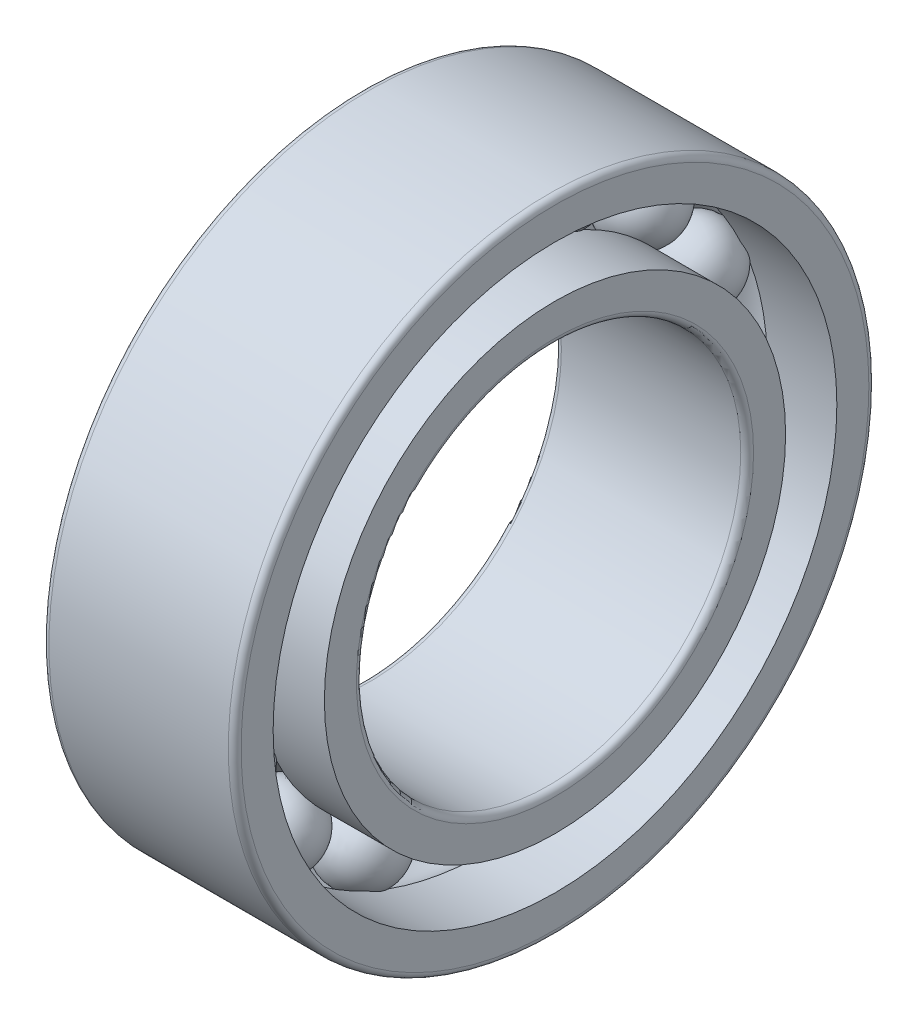
SolidWorks part; units mm, degrees
ref_plane "Plane1" through (0, 0, 0) normal (0, 0, 1) x (1, 0, 0)
ref_plane "Plane2" through (0, 0, 0) normal (0, 1, 0) x (1, 0, 0)
ref_plane "Plane3" through (0, 0, 0) normal (1, 0, 0) x (0, 0, -1)
sketch "Clipboard" plane through (0, 0, 0) normal (0, 0, 1) x (1, 0, 0)
  line L0 (-10, 0) -> (10, 0) construction
  line L1 (0, 0) -> (21.4945, -6.1634)
  line L2 (0, 0) -> (3.845, 1.1025)
  line L3 (0, 0) -> (21.4945, -6.1634)
  line L4 (0, 0) -> (-22.3573, -0.3902)
  dimension "BallCLRad" = 4
sketch "CagSpiSke" plane through (0, 0, 0) normal (0, 0, 1) x (1, 0, 0)
  line L0 (0.06, 3.9) -> (0.06, 4.1)
  line L1 (0.06, 4.1) -> (-0.06, 4.1)
  line L2 (-0.06, 4.1) -> (-0.06, 3.9)
  line L3 (-0.06, 3.9) -> (0.06, 3.9)
  line L4 (-20.6375, 0) -> (20.6375, 0) construction
  line L5 (0, 0) -> (0, 23.7692) construction
  dimension "OD" = 8.2
  dimension "ID" = 7.8
revolve "CageSpine" add sketch "CagSpiSke" angle 0.001 about L4 reverse direction yes
ref_axis "Axis1" through (-50, 0, 0) along (1, 0, 0)
sketch "CagBalSke" plane through (0, 0, 0) normal (0, 0, 1) x (1, 0, 0)
  line L0 (-0.66, 4) -> (0.66, 4)
  line L1 (-1.905, 4) -> (1.905, 4) construction
  line L2 (-10, 0) -> (10, 0) construction
  line L3 (0, 0) -> (0, 24) construction
  arc A0 (0.66, 4) -> (-0.66, 4) centre (0, 4) cw
  dimension "BallCLRad" = 4
revolve "CageBall" [suppressed] add sketch "CagBalSke" angle 360 about L1 reverse direction yes
pattern_circular "CageBalls" [suppressed] count 16 every 22.5 about axis through (-50, 0, 0) along (1, 0, 0)
sketch "CagTrmODSke" plane through (0, 0, 0) normal (0, 0, 1) x (1, 0, 0)
  line L0 (0.661, 4.1) -> (0.661, 4.661)
  line L1 (0.661, 4.661) -> (-0.661, 4.661)
  line L2 (-0.661, 4.661) -> (-0.661, 4.1)
  line L3 (-0.661, 4.1) -> (0.661, 4.1)
  line L4 (-20.6375, 0) -> (20.6375, 0) construction
  line L5 (0, 0) -> (0, 25) construction
  dimension "Width" = 1.322
  dimension "ID" = 8.2
  dimension "OD" = 9.322
revolve "CageTrimOD" [suppressed] cut sketch "CagTrmODSke" angle 360 about L4 reverse direction yes
sketch "CagTrmIDSke" plane through (0, 0, 0) normal (0, 0, 1) x (1, 0, 0)
  line L0 (0.661, 3.341) -> (0.661, 3.9)
  line L1 (0.661, 3.9) -> (-0.661, 3.9)
  line L2 (-0.661, 3.9) -> (-0.661, 3.341)
  line L3 (-0.661, 3.341) -> (0.661, 3.341)
  line L4 (-20.6375, 0) -> (20.6375, 0) construction
  line L5 (0, 0) -> (0, 25) construction
  dimension "Width" = 1.322
  dimension "ID" = 6.682
  dimension "OD" = 7.8
revolve "CageTrimID" [suppressed] cut sketch "CagTrmIDSke" angle 360 about L4 reverse direction yes
sketch "BalSimSke" plane through (0, 0, 0) normal (0, 0, 1) x (1, 0, 0)
  line L0 (-10, 0) -> (10, 0) construction
  line L1 (-10, 4) -> (10, 4) construction
  line L2 (0, 0) -> (0, 23) construction
  circle A0 centre (0, 4) radius 0.6
  dimension "BallCLRad" = 4
  dimension "Ball_diameter" = 1.2
revolve "BallsSimplified" [suppressed] add sketch "BalSimSke" angle 360 about L0
sketch "BalDetSke" plane through (0, 0, 0) normal (0, 0, 1) x (1, 0, 0)
  line L0 (-0.6, 4) -> (0.6, 4)
  line L1 (-1.905, 4) -> (1.905, 4) construction
  line L2 (0, 0) -> (0, 25) construction
  arc A0 (0.6, 4) -> (-0.6, 4) centre (0, 4) cw
  dimension "BallCLRad" = 4
  dimension "Ball_diameter" = 1.2
revolve "BallDetailed" add sketch "BalDetSke" angle 360 about L1 reverse direction yes
sketch "InnRacSke" plane through (0, 0, 0) normal (0, 0, 1) x (1, 0, 0)
  line L0 (-0.4131, 3.6) -> (-1.5, 3.6)
  line L1 (-1.5, 3.6) -> (-1.5, 3.1)
  line L2 (-1.4, 3) -> (1.4, 3)
  line L3 (1.5, 3.1) -> (1.5, 3.6)
  line L4 (1.5, 3.6) -> (0.4131, 3.6)
  line L5 (-20.6375, 0) -> (20.6375, 0) construction
  line L6 (0, 0) -> (0, 30) construction
  arc A0 (-1.5, 3.1) -> (-1.4, 3) centre (-1.4, 3.1) ccw
  arc A1 (1.4, 3) -> (1.5, 3.1) centre (1.4, 3.1) ccw
  arc A2 (0.4131, 3.6) -> (-0.4131, 3.6) centre (0, 4) cw
  dimension "BallCLRad" = 4
  dimension "Fillet_radius" = 0.1
  dimension "Ball_diameter" = 1.15
  dimension "ID" = 6
  dimension "OD" = 7.2
  dimension "Width" = 3
revolve "InnerRace" add sketch "InnRacSke" angle 360 about L5 reverse direction yes
sketch "OutRacSke" plane through (0, 0, 0) normal (0, 0, 1) x (1, 0, 0)
  line L0 (-0.4131, 4.4) -> (-1.5, 4.4)
  line L1 (-1.5, 4.4) -> (-1.5, 4.9)
  line L2 (-1.4, 5) -> (1.4, 5)
  line L3 (1.5, 4.9) -> (1.5, 4.4)
  line L4 (1.5, 4.4) -> (0.4131, 4.4)
  line L5 (-20.6375, 0) -> (20.6375, 0) construction
  line L6 (0, 0) -> (0, 30) construction
  arc A0 (-1.5, 4.9) -> (-1.4, 5) centre (-1.4, 4.9) cw
  arc A1 (1.4, 5) -> (1.5, 4.9) centre (1.4, 4.9) cw
  arc A2 (0.4131, 4.4) -> (-0.4131, 4.4) centre (0, 4) ccw
  dimension "BallCLRad" = 4
  dimension "Fillet_radius" = 0.1
  dimension "Ball_diameter" = 1.15
  dimension "Width" = 3
revolve "OuterRace" add sketch "OutRacSke" angle 360 about L5 reverse direction yes
pattern_circular "BallsDetailed" count 16 every 22.5 about axis through (-50, 0, 0) along (1, 0, 0) of "BallDetailed"
equation "\"BallCLRad@Clipboard\" = ( \"OD@OutRacSke\" + \"ID@InnRacSke\" ) / 4"
equation "\"BallCLRad@BalSimSke\" = \"BallCLRad@Clipboard\""
equation "\"BallCLRad@BalDetSke\" = \"BallCLRad@Clipboard\""
equation "\"BallCLRad@InnRacSke\" = \"BallCLRad@Clipboard\""
equation "\"BallCLRad@OutRacSke\" = \"BallCLRad@Clipboard\""
equation "\"Ball_diameter@InnRacSke\" = \"Ball_diameter@BalDetSke\" - 0.05"
equation "\"Ball_diameter@OutRacSke\" = \"Ball_diameter@BalDetSke\" - 0.05"
equation "\"Ball_diameter@BalSimSke\" = \"Ball_diameter@BalDetSke\""
equation "\"Width@OutRacSke\" = \"Width@InnRacSke\""
equation "\"Fillet_radius@OutRacSke\" = \"Fillet_radius@InnRacSke\""
equation "\"Max_count@Clipboard\" = int( 3.14159265 / atn(( \"Ball_diameter@BalDetSke\" / 2) / sqr( \"BallCLRad@Clipboard\"  *  \"BallCLRad@Clipboard\" - ( \"Ball_diameter@BalDetSke\" / 2) *  ( \"Ball_diameter@BalDetSke\" / 2))))"
equation "\"Max_count@Clipboard\" = ((sgn( \"Max_count@Clipboard\" - \"Count@Clipboard\" )-1)*( \"Max_count@Clipboard\" - \"Count@Clipboard\" ))/-2+ \"Count@Clipboard\""
equation "\"Count@BallsDetailed\" = int( \"Show_count@Clipboard\" ) "
equation "\"Count@BallsDetailed\" = ((sgn( \"Count@BallsDetailed\" - \"Max_count@Clipboard\" )-1)*( \"Count@BallsDetailed\" - \"Max_count@Clipboard\" ))/-2+ \"Max_count@Clipboard\""
equation "\"Count@BallsDetailed\" = ((sgn( \"Count@BallsDetailed\" - \"Min_count@Clipboard\" )+1)*( \"Count@BallsDetailed\" - \"Min_count@Clipboard\"))/2 +\"Min_count@Clipboard\""
equation "\"Angle@BallsDetailed\" = 360.0 / \"Max_count@Clipboard\""
equation "\"BallCLRad@CagBalSke\" = \"BallCLRad@Clipboard\""
equation "\"Count@CageBalls\" = \"Count@BallsDetailed\""
equation "\"Angle@CageBalls\" = \"Angle@BallsDetailed\""
equation "\"Angle@CageSpine\" =  \"Angle@CageBalls\" * ( \"Count@CageBalls\" -1 + int( \"Count@CageBalls\" / \"Max_count@Clipboard\" ) )  + 0.001 -  int( \"Count@CageBalls\" / \"Max_count@Clipboard\" ) * 0.001"
equation "\"Angle@CageSpine\" =  \"Angle@CageSpine\" * int( \"Min_count@Clipboard\" / 2) + int(1 / \"Min_count@Clipboard\")  * 0.001"
equation "\"CageWallOD@CagBalSke\" =  \"Ball_diameter@BalDetSke\" * 1.1"
equation "\"Thickness@CagSpiSke\" =  \"Ball_diameter@BalDetSke\" * 0.1"
equation "\"OD@CagTrmODSke\" = \"BallCLRad@Clipboard\" * 2 + \"CageWallOD@CagBalSke\" + 0.002"
equation "\"ID@CagTrmODSke\" = \"BallCLRad@Clipboard\" * 2 + \"Ball_diameter@BalDetSke\" / 6"
equation "\"OD@CagTrmIDSke\" = \"BallCLRad@Clipboard\" * 2 - \"Ball_diameter@BalDetSke\" / 6"
equation "\"ID@CagTrmIDSke\" = \"BallCLRad@Clipboard\" * 2 - \"CageWallOD@CagBalSke\" + 0.002"
equation "\"OD@CagSpiSke\" = \"ID@CagTrmODSke\""
equation "\"ID@CagSpiSke\" = \"OD@CagTrmIDSke\""
equation "\"Width@CagTrmODSke\" = \"CageWallOD@CagBalSke\" + 0.002"
equation "\"Width@CagTrmIDSke\" = \"CageWallOD@CagBalSke\" + 0.002"
